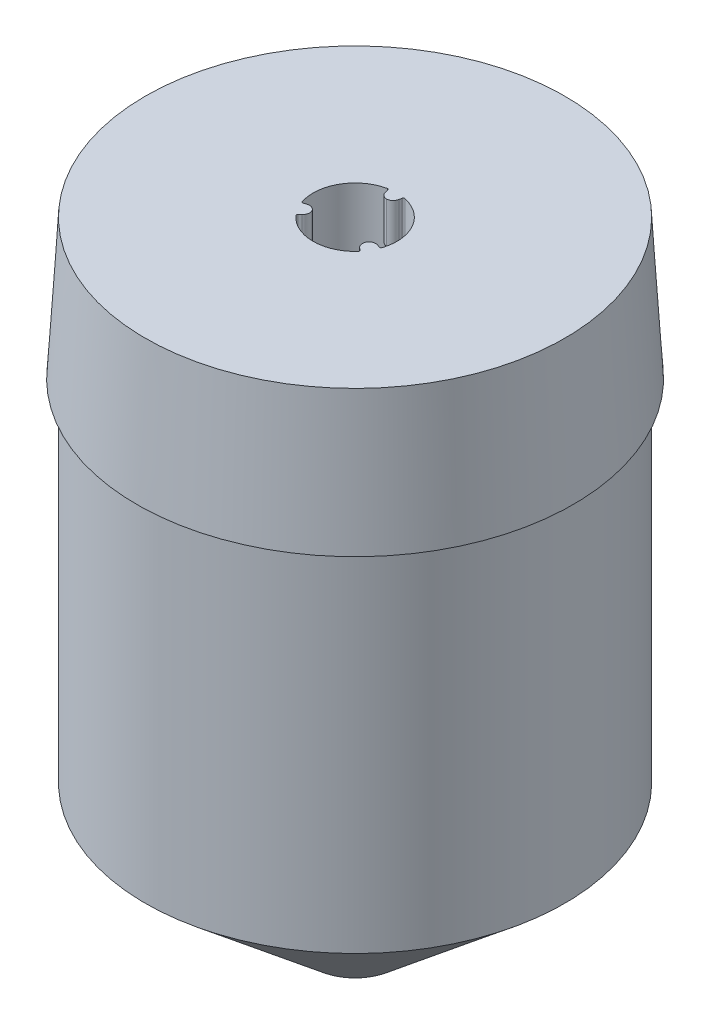
SolidWorks part; units mm, degrees
ref_plane "Front Plane" through (0, 0, 0) normal (0, 0, 1) x (1, 0, 0)
ref_plane "Top Plane" through (0, 0, 0) normal (0, 1, 0) x (1, 0, 0)
ref_plane "Right Plane" through (0, 0, 0) normal (1, 0, 0) x (0, 0, -1)
sketch "Sketch1" plane through (0, 0, 0) normal (0, 0, 1) x (1, 0, 0)
  line L0 (0, 21.4945) -> (0, -21.4945) construction
  line L1 (-33.4391, 0) -> (33.4391, 0) construction
  line L2 (-3, 0) -> (-15, 10)
  line L3 (-15, 10) -> (-15, 35)
  line L7 (-3, 45) -> (-3, 0)
  line L8 (-13.4, 43.4) -> (-4.6, 43.4)
  line L9 (-4.6, 43.4) -> (-4.6, 10.9)
  line L11 (-13.4, 10.9) -> (-13.4, 43.4)
  line L12 (-15, 45) -> (-3, 45)
  line L15 (-15, 35) -> (-15.6, 35)
  line L16 (-15.6, 35) -> (-15, 45)
  line L17 (-13.4, 10.9) -> (-4.6, 10.9)
  dimension "D1" = 3
  dimension "D2" = 45
  dimension "D3" = 15
  dimension "D4" = 0.6
  dimension "D5" = 10
  dimension "D6" = 25
  dimension "D7" = 1.6
  dimension "D8" = 1.6
  dimension "D9" = 1.6
  dimension "D10" = 32.5
  dimension "D12" = 12
revolve "Revolve1" add sketch "Sketch1" angle 360 about L0
ref_plane "Plane4" through (0, 45, 0) normal (0, 1, 0) x (1, 0, 0)
sketch "Sketch2" plane through (0, 45, 0) normal (0, 1, 0) x (1, 0, 0)
  line L0 (0, 5.4064) -> (0, -5.0961) construction
  line L1 (-0.4, 2.25) -> (0.4, 2.25)
  line L2 (-0.4, 2.25) -> (-0.5251, 2.9537)
  line L3 (0, 0) -> (0.4, 2.25) construction
  line L4 (0.4, 2.25) -> (0.5251, 2.9537)
  line L5 (0, 0) -> (-0.4, 2.25) construction
  line L6 (2.1486, -0.7786) -> (2.8205, -1.0221)
  line L7 (1.7486, -1.4714) -> (2.2954, -1.9316)
  line L8 (2.1486, -0.7786) -> (1.7486, -1.4714)
  line L9 (-1.7486, -1.4714) -> (-2.2954, -1.9316)
  line L10 (-2.1486, -0.7786) -> (-2.8205, -1.0221)
  line L11 (-1.7486, -1.4714) -> (-2.1486, -0.7786)
  circle A0 centre (0, 0) radius 2.25 construction
  arc A2 (0.5251, 2.9537) -> (-0.5251, 2.9537) centre (0, 0) ccw
  arc A3 (2.2954, -1.9316) -> (2.8205, -1.0221) centre (0, 0) ccw
  arc A4 (-2.8205, -1.0221) -> (-2.2954, -1.9316) centre (0, 0) ccw
  circle A5 centre (0, 0) radius 3 construction
  point P7 (0, 2.25)
  point P25 (0, 0)
  dimension "D1" = 4.5
  dimension "D2" = 0.8
  dimension "D3" = 3
extrude "Boss-Extrude1" add sketch "Sketch2" against normal blind 3
ref_plane "Plane2" through (0, 10.9, 0) normal (0, 1, 0) x (1, 0, 0)
sketch "Sketch3" plane through (0, 10.9, 0) normal (0, 1, 0) x (1, 0, 0)
  line L3 (-0.4, 2.25) -> (0.4, 2.25)
  line L4 (0.4, 2.25) -> (0.5251, 2.9537)
  line L5 (-0.5251, 2.9537) -> (-0.4, 2.25)
  line L6 (-0.4, 2.25) -> (0.4, 2.25)
  line L7 (0.4, 2.25) -> (0.5251, 2.9537)
  line L8 (-0.5251, 2.9537) -> (-0.4, 2.25)
  line L9 (-2.2954, -1.9316) -> (-1.7486, -1.4714)
  line L10 (-2.1486, -0.7786) -> (-2.8205, -1.0221)
  line L11 (-1.7486, -1.4714) -> (-2.1486, -0.7786)
  line L12 (-2.2954, -1.9316) -> (-1.7486, -1.4714)
  line L13 (-2.1486, -0.7786) -> (-2.8205, -1.0221)
  line L14 (-1.7486, -1.4714) -> (-2.1486, -0.7786)
  line L15 (1.7486, -1.4714) -> (2.2954, -1.9316)
  line L16 (2.1486, -0.7786) -> (1.7486, -1.4714)
  line L17 (2.8205, -1.0221) -> (2.1486, -0.7786)
  line L18 (1.7486, -1.4714) -> (2.2954, -1.9316)
  line L19 (2.1486, -0.7786) -> (1.7486, -1.4714)
  line L20 (2.8205, -1.0221) -> (2.1486, -0.7786)
  arc A1 (0.5251, 2.9537) -> (-0.5251, 2.9537) centre (0, 0) ccw
  arc A2 (0.5251, 2.9537) -> (-0.5251, 2.9537) centre (0, 0) ccw
  arc A3 (-2.8205, -1.0221) -> (-2.2954, -1.9316) centre (0, 0) ccw
  arc A4 (-2.8205, -1.0221) -> (-2.2954, -1.9316) centre (0, 0) ccw
  arc A5 (2.2954, -1.9316) -> (2.8205, -1.0221) centre (0, 0) ccw
  arc A6 (2.2954, -1.9316) -> (2.8205, -1.0221) centre (0, 0) ccw
  dimension "D1" = 0
  dimension "D2" = 0
  dimension "D3" = 0
extrude "Boss-Extrude2" add sketch "Sketch3" against normal blind 3
fillet "Fillet1" radius 0.5 12 edges at (-1.7486, 9.4, 1.4714) (1.7486, 9.4, 1.4714) (2.1486, 9.4, 0.7786) (-2.1486, 9.4, 0.7786) (2.1486, 43.5, 0.7786) (-2.1486, 43.5, 0.7786) (-1.7486, 43.5, 1.4714) (1.7486, 43.5, 1.4714) (0.4, 9.4, -2.25) (-0.4, 9.4, -2.25) (0.4, 43.5, -2.25) (-0.4, 43.5, -2.25)
fillet "Fillet2" radius 0.1 52 edges at (0.5251, 43.5, -2.9537) (-0.5251, 43.5, -2.9537) (2.2954, 43.5, 1.9316) (2.8205, 43.5, 1.0221) (-2.8205, 43.5, 1.0221) (-2.2954, 43.5, 1.9316) (-2.8205, 9.4, 1.0221) (-2.2954, 9.4, 1.9316) (2.8205, 9.4, 1.0221) (2.2954, 9.4, 1.9316) (0.5251, 9.4, -2.9537) (-0.5251, 9.4, -2.9537) (0, 42, -3) (-0.4992, 42, -2.8081) (-0.3094, 42, -2.3729) (0.3094, 42, -2.3729) (0.4992, 42, -2.8081) (2.1823, 42, 1.8364) (2.5981, 42, 1.5) (2.6815, 42, 0.9717) (2.2097, 42, 0.9185) (1.9003, 42, 1.4544) (-2.5981, 42, 1.5) (-2.1823, 42, 1.8364) (-1.9003, 42, 1.4544) (-2.2097, 42, 0.9185) (-2.6815, 42, 0.9717) (2.5981, 7.9, 1.5) (2.6815, 7.9, 0.9717) (2.2097, 7.9, 0.9185) (1.9003, 7.9, 1.4544) (2.1823, 7.9, 1.8364) (-2.5981, 10.9, 1.5) (-2.6815, 10.9, 0.9717) (-2.2097, 10.9, 0.9185) (-1.9003, 10.9, 1.4544) (-2.1823, 10.9, 1.8364) (2.6815, 10.9, 0.9717) (2.5981, 10.9, 1.5) (2.1823, 10.9, 1.8364) (1.9003, 10.9, 1.4544) (2.2097, 10.9, 0.9185) (-0.4992, 10.9, -2.8081) (0, 10.9, -3) (0.4992, 10.9, -2.8081) (0.3094, 10.9, -2.3729) (-0.3094, 10.9, -2.3729) (0, 7.9, -3) (-0.4992, 7.9, -2.8081) (-0.3094, 7.9, -2.3729) (0.3094, 7.9, -2.3729) (0.4992, 7.9, -2.8081)
